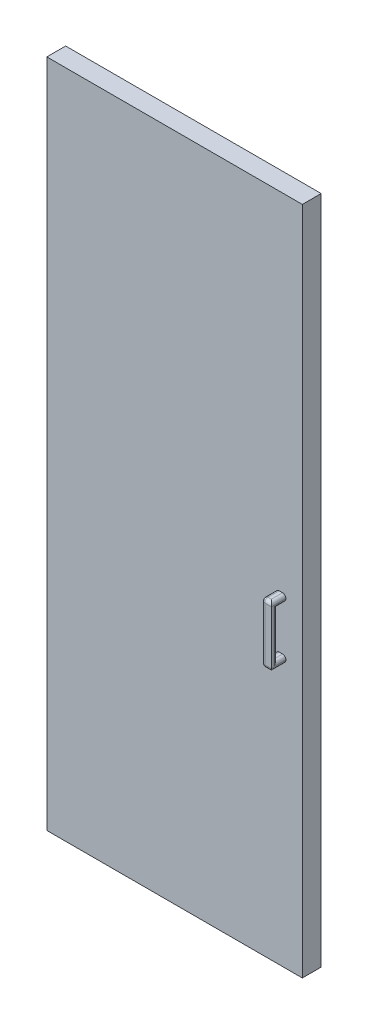
SolidWorks part; units mm, degrees
ref_plane "Front Plane" through (0, 0, 0) normal (0, 0, 1) x (1, 0, 0)
ref_plane "Top Plane" through (0, 0, 0) normal (0, 1, 0) x (1, 0, 0)
ref_plane "Right Plane" through (0, 0, 0) normal (1, 0, 0) x (0, 0, -1)
sketch "Sketch1" plane through (0, 0, 0) normal (0, 0, 1) x (1, 0, 0)
  line L0 (0, 0) -> (0, 18.7953) construction
  line L1 (0, 0) -> (0, 446.2018)
  line L2 (0, 446.2018) -> (-775, 446.2018)
  line L3 (-775, 446.2018) -> (-775, -1585.7982)
  line L4 (-775, -1585.7982) -> (0, -1585.7982)
  line L5 (0, -1585.7982) -> (0, 0)
  line L7 (-178.7641, -553.7982) -> (-148.7641, -553.7982)
  line L8 (-178.7641, -553.7982) -> (-178.7641, -735.7982)
  line L9 (-178.7641, -735.7982) -> (-148.7641, -735.7982)
  line L10 (-148.7641, -553.7982) -> (-148.7641, -735.7982)
  line L11 (-178.7641, -553.7982) -> (-148.7641, -735.7982) construction
  line L12 (-178.7641, -735.7982) -> (-148.7641, -553.7982) construction
  point P9 (-163.7641, -644.7982)
  dimension "D1" = 775
  dimension "D2" = 2032
  dimension "D3" = 30
  dimension "D4" = 182
  dimension "D5" = 850
extrude "Boss-Extrude2" add sketch "Sketch1" along normal blind 57.15 contours L3 L4 L5 L1 L2
sketch "Sketch4" plane through (0, 0, 57.15) normal (0, 0, 1) x (1, 0, 0)
  line L0 (-50, 0) -> (-50, -1857.8255) construction
  line L1 (-775, -1585.7982) -> (0, -1585.7982) construction
  line L2 (-80, -603.7982) -> (-50, -603.7982)
  line L3 (-80, -603.7982) -> (-80, -785.7982)
  line L4 (-80, -785.7982) -> (-50, -785.7982)
  line L5 (-50, -603.7982) -> (-50, -785.7982)
  line L6 (-80, -603.7982) -> (-50, -785.7982) construction
  line L7 (-80, -785.7982) -> (-50, -603.7982) construction
  point P1 (-65, -694.7982)
  dimension "D1" = 50
  dimension "D2" = 30
  dimension "D3" = 182
  dimension "D4" = 800
extrude "Boss-Extrude3" add sketch "Sketch4" along normal blind 44
sketch "Sketch5" plane through (-80, 0, 0) normal (-1, 0, 0) x (0, 0, 1)
  line L0 (57.15, -603.7982) -> (57.15, -785.7982)
  line L1 (57.15, -624.7982) -> (83.15, -624.7982)
  line L2 (83.15, -624.7982) -> (83.15, -764.7982)
  line L3 (83.15, -764.7982) -> (57.15, -764.7982)
  line L4 (57.15, -624.7982) -> (57.15, -764.7982)
  line L5 (101.15, -785.7982) -> (57.15, -785.7982) construction
  dimension "D1" = 140
  dimension "D2" = 21
  dimension "D3" = 26
extrude "Cut-Extrude1" cut sketch "Sketch5" against normal blind 44 contours L3 L2 L1 L0 region at (-80, -694.7982, 70.15)
fillet "Fillet1" radius 10 13 edges at (-80, -694.7982, 83.15) (-80, -603.7982, 79.15) (-80, -624.7982, 70.15) (-50, -603.7982, 79.15) (-50, -624.7982, 70.15) (-50, -694.7982, 83.15) (-50, -764.7982, 70.15) (-50, -785.7982, 79.15) (-80, -785.7982, 79.15) (-80, -764.7982, 70.15) (-80, -694.7982, 101.15) (-65, -785.7982, 101.15) (-65, -603.7982, 101.15)
sketch "Sketch6" plane through (0, 0, 0) normal (0, 0, -1) x (-1, 0, 0)
  line L0 (775, -1585.7982) -> (0, -1585.7982) construction
  line L1 (25, -924.7982) -> (145, -924.7982)
  line L2 (25, -924.7982) -> (25, -464.7982)
  line L3 (25, -464.7982) -> (145, -464.7982)
  line L4 (145, -924.7982) -> (145, -464.7982)
  line L5 (25, -924.7982) -> (145, -464.7982) construction
  line L6 (25, -464.7982) -> (145, -924.7982) construction
  line L7 (0, -1585.7982) -> (0, 446.2018) construction
  point P0 (85, -694.7982)
  dimension "D1" = 120
  dimension "D2" = 891
  dimension "D3" = 460
  dimension "D4" = 25
extrude "Boss-Extrude4" add sketch "Sketch6" along normal blind 10
